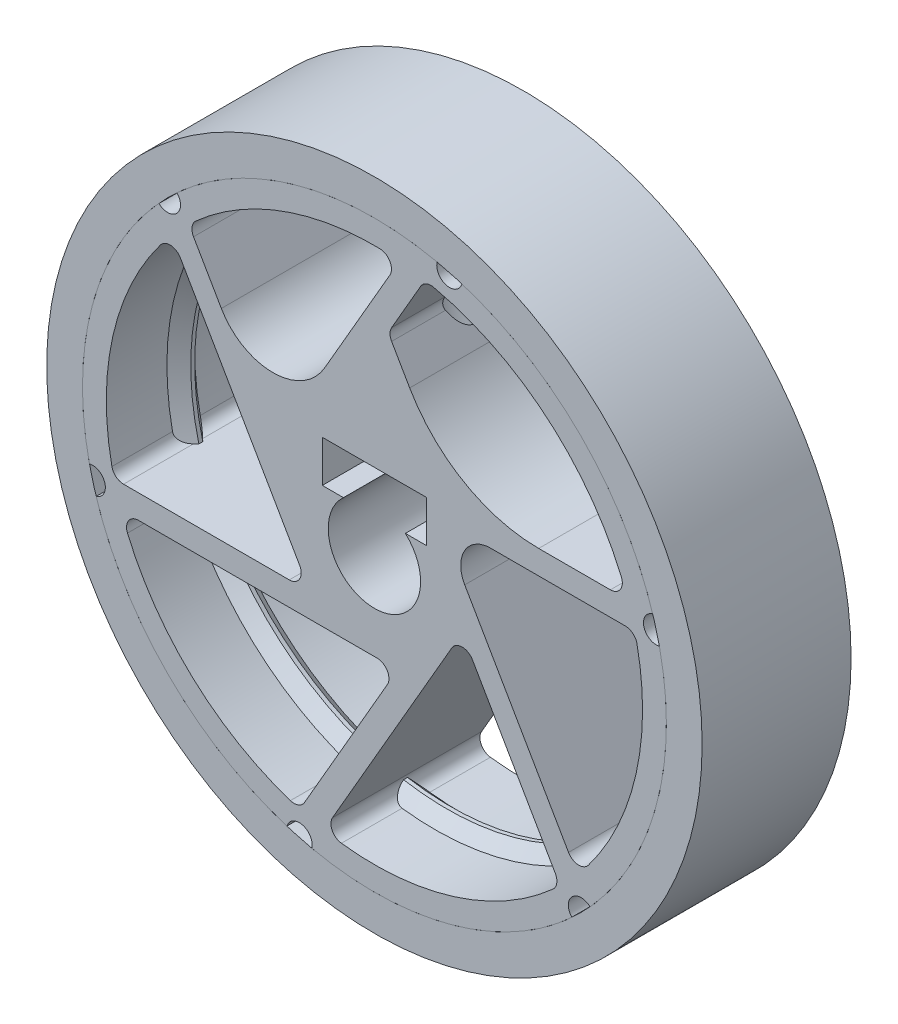
SolidWorks part; units mm, degrees
other "hub"
other "tire-mock"
ref_plane "Front Plane" through (0, 0, 0) normal (0, 0, 1) x (1, 0, 0)
ref_plane "Top Plane" through (0, 0, 0) normal (0, 1, 0) x (1, 0, 0)
ref_plane "Right Plane" through (0, 0, 0) normal (1, 0, 0) x (0, 0, -1)
other "Center of Mass"
sketch "Sketch1" plane through (0, 0, 0) normal (0, 0, 1) x (1, 0, 0)
  line L0 (2.0785, 2.3) -> (3.5, 2.3)
  line L1 (3.5, 2.3) -> (3.5, 5.1)
  line L2 (3.5, 5.1) -> (-3.5, 5.1)
  line L3 (-3.5, 5.1) -> (-3.5, 2.3)
  line L4 (-3.5, 2.3) -> (-2.0785, 2.3)
  line L5 (-1.9261, 2.3) -> (1.9261, 2.3) construction
  line L6 (-6.8127, 0) -> (-13.6123, 11.7773)
  line L7 (3.4064, -5.9) -> (6.8127, 0) construction
  line L8 (6.8127, 0) -> (3.4064, 5.9) construction
  line L9 (3.4064, 5.9) -> (-3.4064, 5.9) construction
  line L10 (-3.4064, 5.9) -> (-6.8127, 0) construction
  line L11 (-6.8127, 0) -> (-3.4064, -5.9) construction
  line L12 (-3.4064, -5.9) -> (3.4064, -5.9) construction
  line L13 (-3.4064, -5.9) -> (-17.0056, -5.9)
  line L14 (3.4064, -5.9) -> (-3.3932, -17.6773)
  line L15 (6.8127, 0) -> (13.6123, -11.7773)
  line L16 (-5.889, 1.6) -> (-12.4633, 12.9871) construction
  line L17 (5.889, -1.6) -> (12.4633, -12.9871)
  line L18 (1.5588, -5.9) -> (-5.0155, -17.2871)
  line L19 (-4.3301, -4.3) -> (-17.4788, -4.3)
  line L20 (3.4064, 5.9) -> (17.0056, 5.9) construction
  line L21 (4.3301, 4.3) -> (17.4788, 4.3)
  line L22 (-12.4633, 12.9871) -> (-6.8127, 3.2)
  line L23 (-6.8127, 3.2) -> (-3.3459, 9.2048)
  line L24 (-3.3459, 9.2048) -> (3.3459, 9.2048) construction
  line L25 (3.3459, 9.2048) -> (5.2539, 5.9)
  line L26 (5.2539, 5.9) -> (17.0056, 5.9)
  line L29 (-6.8127, 0) -> (-4.3301, -4.3)
  line L30 (-3.4064, -5.9) -> (1.5588, -5.9)
  line L31 (3.4064, -5.9) -> (5.889, -1.6)
  line L32 (6.8127, 0) -> (4.3301, 4.3)
  line L33 (-3.3459, 9.2048) -> (1.6863, 17.9208)
  line L34 (3.3932, 17.6773) -> (-1.4983, 9.2048)
  line L35 (3.3459, 9.2048) -> (-1.4983, 9.2048)
  line L36 (11.1297, 5.9) -> (11.1297, 4.3) construction
  line L37 (-0.8298, 13.5628) -> (0.5559, 12.7628) construction
  circle A0 centre (0, 0) radius 3 construction
  circle A1 centre (0, 0) radius 3.1 construction
  arc A2 (-2.0785, 2.3) -> (2.0785, 2.3) centre (0, 0) ccw
  circle A3 centre (0, 0) radius 5.9 construction
  circle A4 centre (0, 0) radius 22 construction
  circle A6 centre (0, 0) radius 19.6
  circle A7 centre (0, 0) radius 18 construction
  arc A8 (1.6863, 17.9208) -> (-12.4633, 12.9871) centre (0, 0) ccw
  arc A9 (-13.6123, 11.7773) -> (-17.4788, -4.3) centre (0, 0) ccw
  arc A10 (-5.0155, -17.2871) -> (-17.0056, -5.9) centre (0, 0) cw
  arc A11 (12.4633, -12.9871) -> (-3.3932, -17.6773) centre (0, 0) cw
  arc A12 (17.4788, 4.3) -> (13.6123, -11.7773) centre (0, 0) cw
  arc A13 (17.0056, 5.9) -> (3.3932, 17.6773) centre (0, 0) ccw
  point P13 (0, -3)
  point P43 (0, 9.2048)
  point P55 (-19.6, 0)
  point P56 (19.6, 0)
  point P58 (0, -19.6)
  point P59 (0, 19.6)
  point P61 (-18, 0)
  dimension "D1" = 6
  dimension "D7" = 44
  dimension "D3" = 7
  dimension "D4" = 2.8
  dimension "D5" = 5.3
  dimension "D6" = 0.8
  dimension "D10" = 1.6
  dimension "D11" = 4.1048
  dimension "D12" = 1.6
  dimension "D2" = 0.1
  dimension "D8" = 2.4
  dimension "D9" = 1.6
extrude "Boss-Extrude1" add sketch "Sketch1" along normal blind 10
ref_axis "Axis1" through (0, 0, 10) along (0, 0, -1)
sketch "Sketch9" plane through (0, 0, 0) normal (0, 0, -1) x (-1, 0, 0)
  line L0 (-3.3459, 9.2048) -> (-0.9238, 13.4)
  line L1 (-3.3459, 9.2048) -> (-5.2539, 5.9) construction
  line L2 (-3.3932, 17.6773) -> (1.4983, 9.2048) construction
  line L3 (-0.9238, 13.4) -> (1.4983, 9.2048)
  line L4 (1.4983, 9.2048) -> (-3.3459, 9.2048)
extrude "Boss-Extrude3" add sketch "Sketch9" against normal up to surface (10 mm away) up to face at (19.6, 0, 10)
sketch "Sketch10" plane through (0, 0, 0) normal (0, 0, -1) x (-1, 0, 0)
  line L0 (2.3094, 11) -> (6.6114, 18.4513)
  line L1 (3.3459, 9.2048) -> (-1.6863, 17.9208) construction
  line L2 (6.6114, 18.4513) -> (10.2298, 16.7186)
  line L3 (10.2298, 16.7186) -> (4.6188, 7)
  line L4 (4.6188, 7) -> (2.3094, 11)
  line L5 (-3.3459, 9.2048) -> (-5.2539, 5.9) construction
  circle A0 centre (0, 0) radius 19.6 construction
  dimension "D1" = 4
  dimension "D2" = 4
extrude "Boss-Extrude6" [suppressed] add sketch "Sketch10" against normal up to surface (10 mm away) up to face at (7.0386, 11.1752, 10)
fillet "Fillet1" radius 0.8 4 edges at (5.889, -1.6, 5) (1.5588, -5.9, 5) (-4.3301, -4.3, 5) (0.9238, 13.4, 5)
fillet "Fillet2" radius 0.8 6 edges at (13.6123, -11.7773, 5) (17.0056, 5.9, 5) (-13.6123, 11.7773, 5) (-17.0056, -5.9, 5) (-3.3932, -17.6773, 5) (1.6863, 17.9208, 5)
fillet "Fillet3" radius 0.8 6 edges at (-17.4788, -4.3, 5) (-12.4633, 12.9871, 5) (17.4788, 4.3, 5) (12.4633, -12.9871, 5) (-5.0155, -17.2871, 5) (3.3932, 17.6773, 5)
sketch "Sketch8" [suppressed] plane through (0, 0, 10) normal (0, 0, 1) x (1, 0, 0)
  line L1 (-3.4613, 18.0715) -> (3.4613, 18.0715)
  line L2 (-3.4613, 18.0715) -> (-3.4613, 9.4048)
  line L3 (-3.4613, 9.4048) -> (3.4613, 9.4048)
  line L4 (3.4613, 18.0715) -> (3.4613, 9.4048)
  line L5 (0, 9.4048) -> (0, 18.0715) construction
  line L6 (-3.4613, 13.7382) -> (3.4613, 13.7382) construction
  circle A0 centre (0, 0) radius 18.4 construction
  point P0 (0, 13.7382)
extrude "Boss-Extrude2" [suppressed] add sketch "Sketch8" against normal up to surface (10 mm away) up to face at (6.9232, 11.6873, 0)
sketch "Sketch2" plane through (0, 5.1, 0) normal (0, -1, 0) x (1, 0, 0)
  line L0 (0, 10) -> (0, 0) construction
  line L1 (3.5, 10) -> (-3.5, 10) construction
  line L2 (3.5, 0) -> (-3.5, 0) construction
  circle A0 centre (0, 5) radius 1.8
  dimension "D1" = 3.6
extrude "Cut-Extrude1" cut sketch "Sketch2" against normal up to surface (12.8098 mm away) up to face at (10.9125, 13.0451, 5)
sketch "Sketch5" plane through (0, 0, 0) normal (0, 1, 0) x (1, 0, 0)
  line L0 (-19.6, -3.6) -> (-19.6, -6.4)
  line L3 (-19.6, -3.6) -> (-18.8, -4.4)
  line L4 (-18.8, -4.4) -> (-18.8, -5.6)
  line L5 (-18.8, -5.6) -> (-19.6, -6.4)
  point P3 (-19.6, -5)
  dimension "D1" = 0.8
  dimension "D2" = 45
  dimension "D3" = 1.2
sketch "Sketch7" plane through (0, 0, 0) normal (0, 1, 0) x (1, 0, 0)
  line L0 (-19.6, -2.4686) -> (-19.6, -7.5314)
  line L1 (-19.6, -7.5314) -> (-17.2, -5.1314)
  line L2 (-17.2, -5.1314) -> (-17.2, -4.8686)
  line L3 (-17.2, -4.8686) -> (-19.6, -2.4686)
  line L4 (-18.8, -5.6) -> (-19.6, -6.4) construction
  line L5 (-19.6, -3.6) -> (-19.6, -6.4) construction
  line L6 (-18.8, -4.4) -> (-18.8, -5.6) construction
  point P6 (-19.6, -5)
  dimension "D1" = 1.6
  dimension "D2" = 0.8
revolve "Revolve1" add sketch "Sketch7" angle 360 about axis through (0, 0, 10) along (0, 0, -1)
sketch "Sketch6" plane through (0, 5.1, 0) normal (0, -1, 0) x (1, 0, 0)
  circle A0 centre (0, 5) radius 1.4
  dimension "D1" = 2.8
extrude "Cut-Extrude3" cut sketch "Sketch6" against normal through all
sketch "Sketch3" plane through (0, 0, 10) normal (0, 0, 1) x (1, 0, 0)
  line L0 (2.4826, -5.9) -> (-5.0457, -18.9394) construction
  line L1 (-3.4064, -5.9) -> (3.4064, -5.9) construction
  line L2 (1.5588, -5.9) -> (-5.0155, -17.2871) construction
  line L3 (1.5588, -5.9) -> (3.4064, -5.9) construction
  circle A0 centre (-5.0457, -18.9394) radius 0.8625
  circle A1 centre (0, 0) radius 19.6 construction
  circle A2 centre (0, 0) radius 18 construction
  circle A3 centre (-18.9249, -5.1) radius 0.8625
  circle A4 centre (-13.8792, 13.8394) radius 0.8625
  circle A5 centre (5.0457, 18.9394) radius 0.8625
  circle A6 centre (18.9249, 5.1) radius 0.8625
  circle A7 centre (13.8792, -13.8394) radius 0.8625
  point P14 (2.4826, -5.9)
  point P15 (-4.6145, -18.1925)
  point P16 (-4.2145, -17.4997)
  point P32 (0, 0)
  dimension "D1" = 0.8
  dimension "D2" = 6
extrude "Cut-Extrude2" cut sketch "Sketch3" against normal through all
revolve "Cut-Revolve2" cut sketch "Sketch5" angle 360 about axis through (0, 0, 10) along (0, 0, -1)
sketch "Sketch11" plane through (0, 0, 10) normal (0, 0, 1) x (1, 0, 0)
  circle A0 centre (0, 0) radius 22 construction
  circle A1 centre (0, 0) radius 22
  circle A2 centre (0, 0) radius 19.6 construction
  circle A3 centre (0, 0) radius 19.6
extrude "Boss-Extrude7" add sketch "Sketch11" against normal up to surface (10 mm away) separate body up to face at (6.9232, 11.6873, 0)
sketch "Sketch12" plane through (0, 0, 0) normal (0, 0, -1) x (-1, 0, 0)
  line L1 (-3.4064, -5.9) -> (3.3932, -17.6773) construction
  line L2 (-5.889, -1.6) -> (-12.4633, -12.9871) construction
  circle A0 centre (-10.2973, -12.6355) radius 1.7 construction
  circle A2 centre (0.6281, -16.2879) radius 1.7 construction
  arc A3 (-12.4633, -12.9871) -> (3.3932, -17.6773) centre (0, 0) ccw construction
  arc A4 (-8.8307, -13.4951) -> (-1.0607, -16.0926) centre (-5.2191, -15.6119) cw
  arc A5 (-8.8307, -13.4951) -> (-11.3713, -13.9533) centre (-10.2973, -12.6355) cw
  arc A6 (-1.0607, -16.0926) -> (0.6936, -17.9866) centre (0.6281, -16.2879) ccw
  arc A7 (-11.3713, -13.9533) -> (0.6936, -17.9866) centre (0, 0) ccw
  dimension "D1" = 3.4
extrude "Boss-Extrude8" [suppressed] add sketch "Sketch12" against normal up to surface (10 mm away) up to face at (0, 0, 10)
fillet "Fillet4" radius 10 1 edges at (5.2539, 5.9, 5)
fillet "Fillet5" radius 4 1 edges at (-6.8127, 3.2, 5)
fillet "Fillet6" radius 2 1 edges at (4.3301, 4.3, 5)
